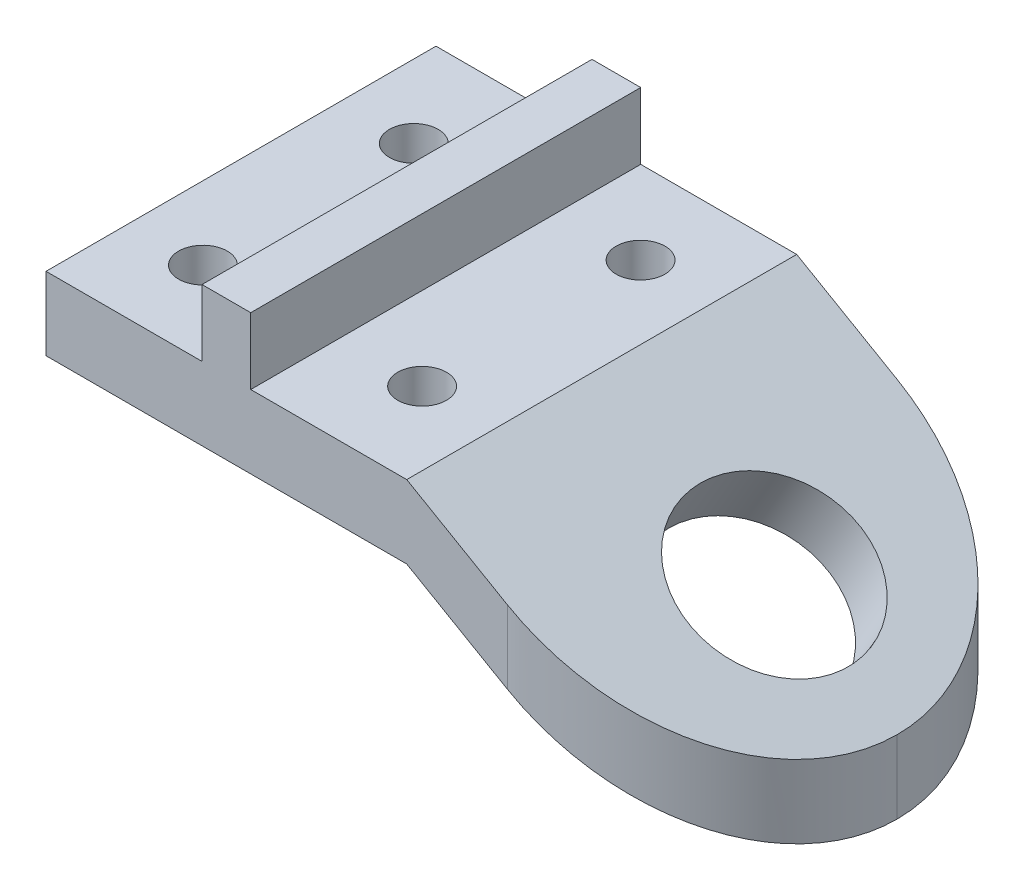
SolidWorks part; units mm, degrees
ref_plane "Front Plane" through (0, 0, 0) normal (0, 0, 1) x (1, 0, 0)
ref_plane "Top Plane" through (0, 0, 0) normal (0, 1, 0) x (1, 0, 0)
ref_plane "Right Plane" through (0, 0, 0) normal (1, 0, 0) x (0, 0, -1)
sketch "Sketch2" plane through (0, 0, 0) normal (0, 0, 1) x (1, 0, 0)
  line L0 (-28.4533, 0) -> (45.5467, 0)
  line L1 (45.5467, 0) -> (106.1684, -35)
  line L2 (-28.4533, 0) -> (-28.4533, 15)
  line L3 (-28.4533, 15) -> (3.5467, 15)
  line L4 (3.5467, 15) -> (3.5467, 28.6533)
  line L5 (3.5467, 28.6533) -> (13.5467, 28.6533)
  line L6 (13.5467, 28.6533) -> (13.5467, 15)
  line L7 (13.5467, 15) -> (45.5467, 15)
  line L8 (45.5467, 15) -> (106.1684, -20)
  line L9 (106.1684, -20) -> (106.1684, -35)
  dimension "D1" = 32
  dimension "D2" = 32
  dimension "D3" = 10
  dimension "D4" = 15
  dimension "D5" = 15
  dimension "D6" = 30
  dimension "D7" = 70
  dimension "D8" = 70
extrude "Boss-Extrude1" add sketch "Sketch2" along normal blind 80
fillet "Fillet1" radius 40 2 edges at (106.1684, -27.5, 0) (106.1684, -27.5, 80)
sketch "Sketch3" plane through (0, 0, 0) normal (0, 1, 0) x (1, 0, 0)
  line L0 (-28.4533, -80) -> (-28.4533, 0) construction
  circle A0 centre (-13.4533, -19.5508) radius 5
  circle A1 centre (-13.4533, -62.8021) radius 5
  point P6 (0, 0)
  point P8 (0, 0)
  dimension "D1" = 15
  dimension "D2" = 15
extrude "Cut-Extrude3" cut sketch "Sketch3" along normal up to surface (15 mm away) up to face at (-12.4533, 15, 40)
sketch "Sketch4" plane through (0, 15, 0) normal (0, 1, 0) x (1, 0, 0)
  line L0 (45.5467, -80) -> (45.5467, 0) construction
  circle A0 centre (30.5467, -17.0327) radius 5
  circle A1 centre (30.5467, -61.8436) radius 5
  point P6 (0, 0)
  point P7 (0, 0)
  point P8 (0, 0)
  dimension "D3" = 10
  dimension "D4" = 10
  dimension "D1" = 15
  dimension "D2" = 15
extrude "Cut-Extrude4" cut sketch "Sketch4" against normal blind 80
sketch "Sketch5" plane through (17.8819, 30.9723, 0) normal (0.5, 0.866, 0) x (0.866, -0.5, 0)
  line L0 (31.9446, -80) -> (31.9446, 0) construction
  circle A0 centre (71.9446, -39.23) radius 17.5
  dimension "D2" = 35
  dimension "D1" = 40
extrude "Cut-Extrude5" cut sketch "Sketch5" against normal blind 26
